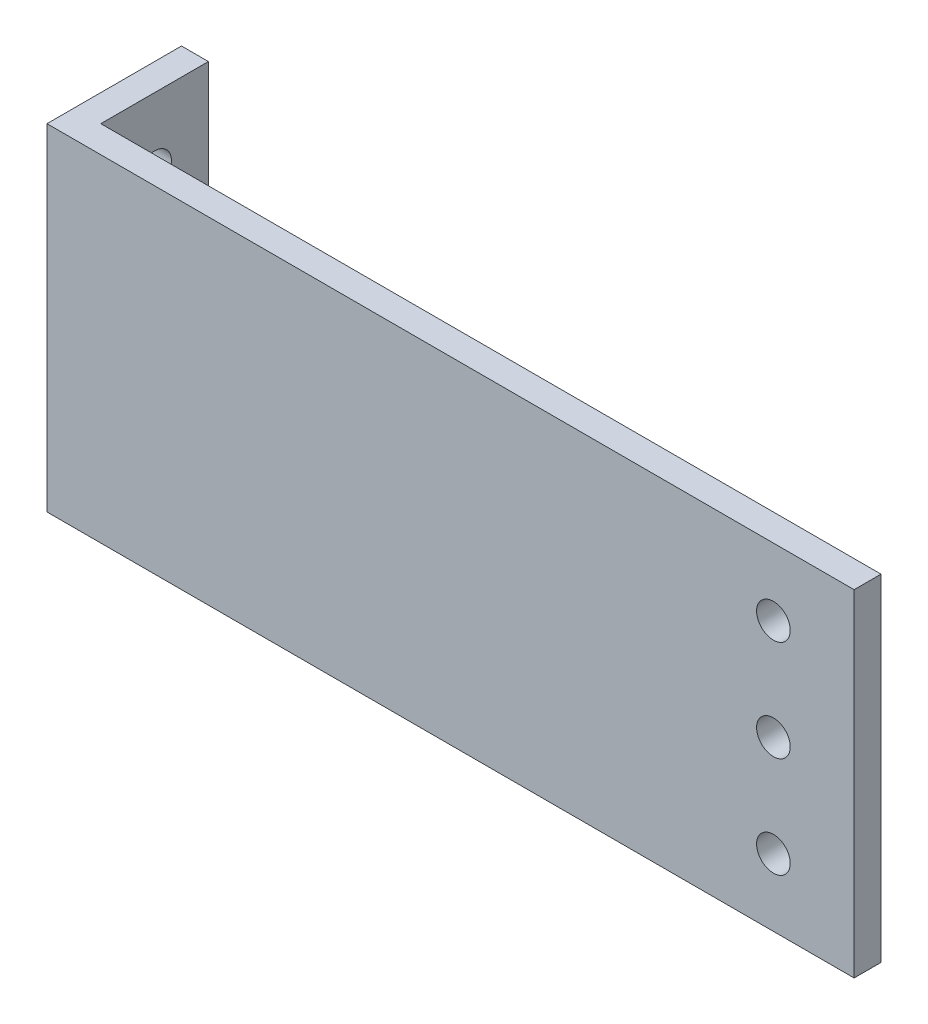
SolidWorks part; units mm, degrees
ref_plane "Спереди" through (0, 0, 0) normal (0, 0, 1) x (1, 0, 0)
ref_plane "Сверху" through (0, 0, 0) normal (0, 1, 0) x (1, 0, 0)
ref_plane "Справа" through (0, 0, 0) normal (1, 0, 0) x (0, 0, -1)
sketch "Эскиз1" plane through (0, 0, 0) normal (0, 1, 0) x (1, 0, 0)
  line L1 (0, 0) -> (120, 0)
  line L2 (0, 0) -> (0, 4)
  line L3 (4, 4) -> (120, 4)
  line L4 (120, 0) -> (120, 4)
  line L6 (0, 4) -> (0, 20)
  line L7 (0, 20) -> (4, 20)
  line L8 (4, 4) -> (4, 20)
  dimension "D1" = 120
  dimension "D2" = 4
  dimension "D3" = 20
  dimension "D4" = 4
extrude "Бобышка-Вытянуть1" add sketch "Эскиз1" along normal blind 50
sketch "Эскиз2" plane through (0, 0, 0) normal (-1, 0, 0) x (0, 0, 1)
  line L0 (-12, 44.9311) -> (-12, 11.555) construction
  line L2 (-20, 0) -> (0, 0) construction
  line L3 (0, 50) -> (0, 0) construction
  circle A0 centre (-12, 40) radius 2.5
  circle A1 centre (-12, 10) radius 2.5
  dimension "D2" = 5
  dimension "D3" = 5
  dimension "D1" = 12
  dimension "D4" = 30
  dimension "D5" = 10
extrude "Вырез-Вытянуть1" cut sketch "Эскиз2" against normal blind 10
sketch "Эскиз3" plane through (0, 0, 0) normal (0, 0, 1) x (1, 0, 0)
  line L0 (108, 46.6766) -> (108, 6.7064) construction
  line L1 (120, 50) -> (120, 0) construction
  line L2 (0, 0) -> (120, 0) construction
  circle A0 centre (108, 40) radius 2.5
  circle A1 centre (108, 10) radius 2.5
  circle A2 centre (108, 25) radius 2.5
  dimension "D2" = 5
  dimension "D3" = 5
  dimension "D6" = 5
  dimension "D1" = 12
  dimension "D4" = 30
  dimension "D5" = 10
  dimension "D7" = 15
extrude "Вырез-Вытянуть2" cut sketch "Эскиз3" against normal blind 10
